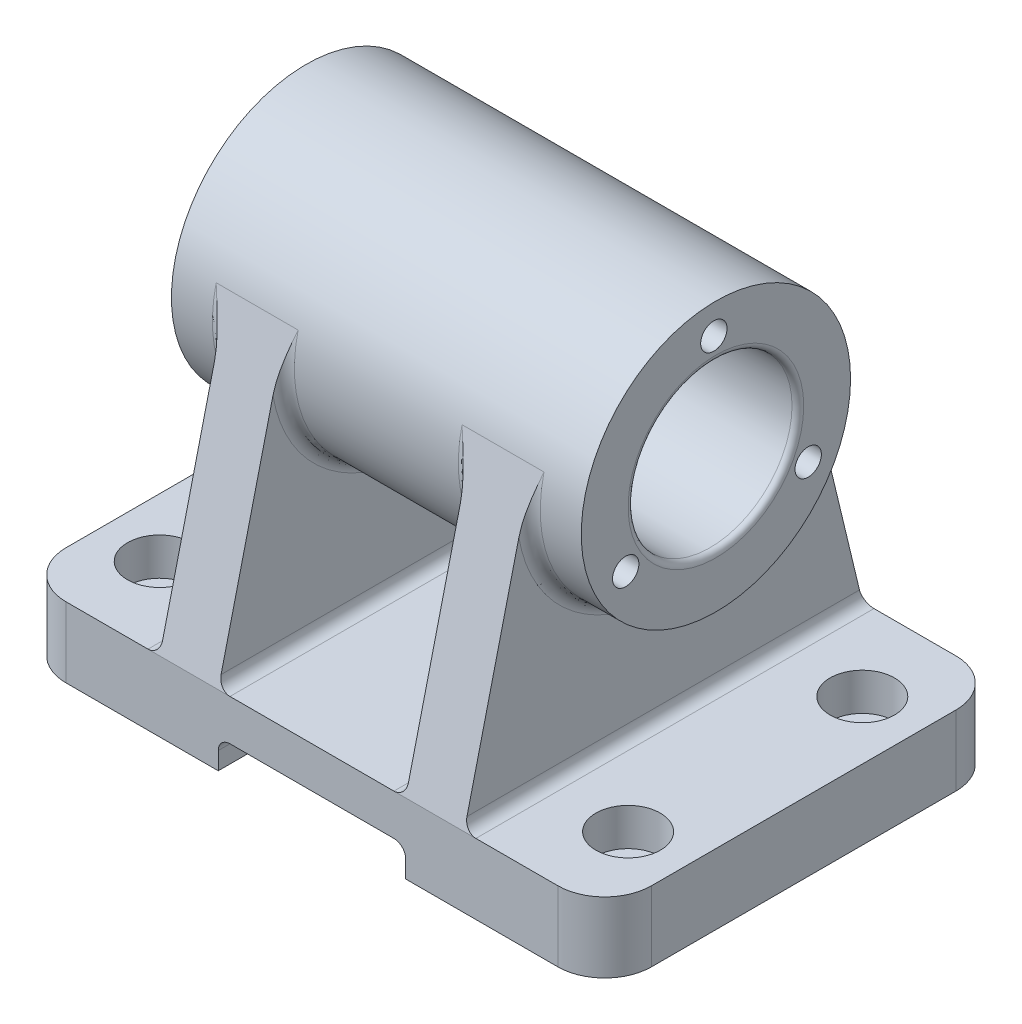
SolidWorks part; units mm, degrees
ref_plane "Front Plane" through (0, 0, 0) normal (0, 0, 1) x (1, 0, 0)
ref_plane "Top Plane" through (0, 0, 0) normal (0, 1, 0) x (1, 0, 0)
ref_plane "Right Plane" through (0, 0, 0) normal (1, 0, 0) x (0, 0, -1)
sketch "Sketch1" plane through (0, 0, 0) normal (0, 1, 0) x (1, 0, 0)
  line L1 (-50, 34) -> (50, 34)
  line L2 (-50, 34) -> (-50, -34)
  line L3 (-50, -34) -> (50, -34)
  line L4 (50, 34) -> (50, -34)
  line L5 (-50, 34) -> (50, -34) construction
  line L6 (-50, -34) -> (50, 34) construction
  point P0 (0, 0)
  dimension "D1" = 100
  dimension "D2" = 68
extrude "Boss-Extrude1" add sketch "Sketch1" along normal blind 12
fillet "Fillet1" radius 8 1 edges at (-50, 6, 34)
fillet "Fillet2" radius 8 1 edges at (50, 6, 34)
fillet "Fillet3" radius 8 1 edges at (50, 6, -34)
fillet "Fillet4" radius 8 1 edges at (-50, 6, -34)
sketch "Sketch2" plane through (0, 0, 34) normal (0, 0, 1) x (1, 0, 0)
  line L2 (-16, 0) -> (-16, 5)
  line L3 (-42, 0) -> (42, 0) construction
  line L4 (-16, 5) -> (16, 5)
  line L5 (16, 5) -> (16, 0)
  line L6 (-16, 0) -> (16, 0)
  dimension "D1" = 5
  dimension "D2" = 32
extrude "Cut-Extrude1" cut sketch "Sketch2" against normal through all
fillet "Fillet5" radius 2 1 edges at (16, 5, 0)
fillet "Fillet6" radius 2 1 edges at (-16, 5, 0)
hole_wizard "CBORE for M6 Hex Socket Head Cap Screw1" positions "Sketch6" profile "Sketch7" counterbore size "M6" standard "ISO"
sketch "Sketch6" plane through (0, 12, 0) normal (0, 1, 0) x (1, 0, 0)
  line L0 (42, 34) -> (-42, 34) construction
  line L2 (50, -26) -> (50, 26) construction
  line L3 (40, 20) -> (40, -20) construction
  point P0 (40, -20)
  point P2 (40, 20)
  dimension "D1" = 40
  dimension "D2" = 14
  dimension "D3" = 10
  dimension "D4" = 10
sketch "Sketch7" plane through (40, 12, 20) normal (1, 0, 0) x (0, 0, 1)
  line L0 (0, 0) -> (0, 16)
  line L1 (0, 16) -> (3.3, 14.0172)
  line L2 (3.3, 14.0172) -> (3.3, 6.4)
  line L3 (3.3, 6.4) -> (5.5, 6.4)
  line L4 (5.5, 6.4) -> (5.5, 0)
  line L5 (5.5, 0) -> (0, 0)
  line L10 (0, 16) -> (-3.3, 14.0172) construction
  line L11 (0, -6.35) -> (0, 107.95) construction
  dimension "Hole Dia." = 6.6
  dimension "Hole Depth" = 16
  dimension "C'Bore Dia." = 11
  dimension "C'Bore Depth" = 6.4
  dimension "Drill Angle" = 118
hole_wizard "CBORE for M6 Hex Socket Head Cap Screw2" positions "Sketch10" profile "Sketch9" counterbore size "M6" standard "ISO"
sketch "Sketch10" plane through (0, 12, 0) normal (0, 1, 0) x (1, 0, 0)
  line L0 (40, 20) -> (-40, 20) construction
  line L1 (-40, 20) -> (-40, -20) construction
  line L2 (-40, -20) -> (40, -20) construction
  line L3 (40, -20) -> (40, 20) construction
  line L5 (-50, 26) -> (-50, -26) construction
  line L7 (42, 34) -> (-42, 34) construction
  line L8 (-42, -34) -> (42, -34) construction
  point P0 (-40, 20)
  point P2 (-40, -20)
  dimension "D1" = 10
  dimension "D2" = 14
  dimension "D3" = 40
  dimension "D4" = 14
sketch "Sketch9" plane through (-40, 12, -20) normal (1, 0, 0) x (0, 0, 1)
  line L0 (0, 0) -> (0, 16)
  line L1 (0, 16) -> (3.3, 14.0172)
  line L2 (3.3, 14.0172) -> (3.3, 6.4)
  line L3 (3.3, 6.4) -> (5.5, 6.4)
  line L4 (5.5, 6.4) -> (5.5, 0)
  line L5 (5.5, 0) -> (0, 0)
  line L10 (0, 16) -> (-3.3, 14.0172) construction
  line L11 (0, -6.35) -> (0, 107.95) construction
  dimension "Hole Dia." = 6.6
  dimension "Hole Depth" = 16
  dimension "C'Bore Dia." = 11
  dimension "C'Bore Depth" = 6.4
  dimension "Drill Angle" = 118
ref_plane "Plane1" through (0, 0, 0) normal (1, 0, 0) x (0, 0, -1)
sketch "Sketch11" plane through (0, 0, 0) normal (1, 0, 0) x (0, 0, -1)
  line L0 (0, 0) -> (0, 55) construction
  line L1 (-26, 0) -> (26, 0) construction
  circle A0 centre (0, 55) radius 23
  circle A1 centre (0, 55) radius 14
  dimension "D1" = 46
  dimension "D2" = 28
  dimension "D3" = 55
extrude "Boss-Extrude5" add sketch "Sketch11" along normal mid plane 70 separate body
ref_plane "Plane2" through (16, 0, 0) normal (1, 0, 0) x (0, 0, -1)
sketch "Sketch15" plane through (16, 0, 0) normal (1, 0, 0) x (0, 0, -1)
  line L0 (22.3621, 60.3793) -> (34, 12)
  line L1 (34, 12) -> (34, 0) construction
  line L2 (34, 12) -> (-34, 12)
  line L3 (-34, 12) -> (-22.3621, 60.3793)
  line L5 (-22.3621, 60.3793) -> (22.3621, 60.3793)
  circle A0 centre (0, 55) radius 23 construction
extrude "Boss-Extrude6" add sketch "Sketch15" along normal blind 10
mirror "Mirror10" about plane through (0, 0, 0) normal (1, 0, 0) of "Boss-Extrude6"
fillet "Fillet7" radius 2 1 edges at (-26, 12, 0)
fillet "Fillet8" radius 2 1 edges at (-26, 32, 0)
fillet "Fillet9" radius 2 1 edges at (-16, 12, 0)
fillet "Fillet10" radius 2 1 edges at (-16, 32, 0)
fillet "Fillet11" radius 2 1 edges at (16, 12, 0)
fillet "Fillet12" radius 2 1 edges at (16, 32, 0)
fillet "Fillet13" radius 2 1 edges at (26, 12, 0)
fillet "Fillet14" radius 2 1 edges at (26, 32, 0)
sketch "Sketch16" plane through (-35, 0, 0) normal (-1, 0, 0) x (0, 0, 1)
  circle A0 centre (0, 55) radius 14
extrude "Cut-Extrude2" cut sketch "Sketch16" against normal through all
hole_wizard "M4 Clearance Hole1" positions "Sketch18" profile "Sketch20" hole size "M4" standard "ISO"
sketch "Sketch18" plane through (-35, 0, 0) normal (-1, 0, 0) x (0, 0, 1)
  circle A0 centre (0, 55) radius 18 construction
  point P0 (0, 73)
  dimension "D1" = 36
sketch "Sketch20" plane through (-35, 73, 0) normal (0, 1, 0) x (0, 0, 1)
  line L0 (0, 0) -> (0, 13.3519)
  line L1 (0, 13.3519) -> (2.25, 12)
  line L2 (2.25, 12) -> (2.25, 0)
  line L5 (2.25, 0) -> (0, 0)
  line L10 (0, 13.3519) -> (-2.25, 12) construction
  line L11 (0, -6.35) -> (0, 107.95) construction
  dimension "Hole Dia." = 4.5
  dimension "Hole Depth" = 12
  dimension "Drill Angle" = 118
pattern_circular "CirPattern1" count 3 over 360 about axis through (-35, 55, 0) along (1, 0, 0) of "M4 Clearance Hole1"
fillet "Fillet15" radius 1 1 edges at (-35, 55, -14)
fillet "Fillet16" radius 1 1 edges at (35, 55, -14)
hole_wizard "M4 Clearance Hole2" positions "3DSketch1" profile "Sketch21" hole size "M4" standard "ISO"
sketch3d "3DSketch1"
  line L0 (0, 0, 0) -> (0, 77.2406, 0) construction
  line L2 (25.5124, 55, 0) -> (50.9753, 55, 0) construction
  circle A0 centre (35, 55, 0) radius 18 construction
  point P0 (35, 72.9965, 0.3527)
  point P12 (53, 55, 0)
  dimension "D1" = 36
sketch "Sketch21" plane through (35, 72.9965, 0.3527) normal (0, 1, 0) x (0, 0, -1)
  line L0 (0, 0) -> (0, 13.3519)
  line L1 (0, 13.3519) -> (2.25, 12)
  line L2 (2.25, 12) -> (2.25, 0)
  line L5 (2.25, 0) -> (0, 0)
  line L10 (0, 13.3519) -> (-2.25, 12) construction
  line L11 (0, -6.35) -> (0, 107.95) construction
  dimension "Hole Dia." = 4.5
  dimension "Hole Depth" = 12
  dimension "Drill Angle" = 118
pattern_circular "CirPattern6" count 3 over 360 about axis through (35, 55, 0) along (1, 0, 0) of "M4 Clearance Hole2"
